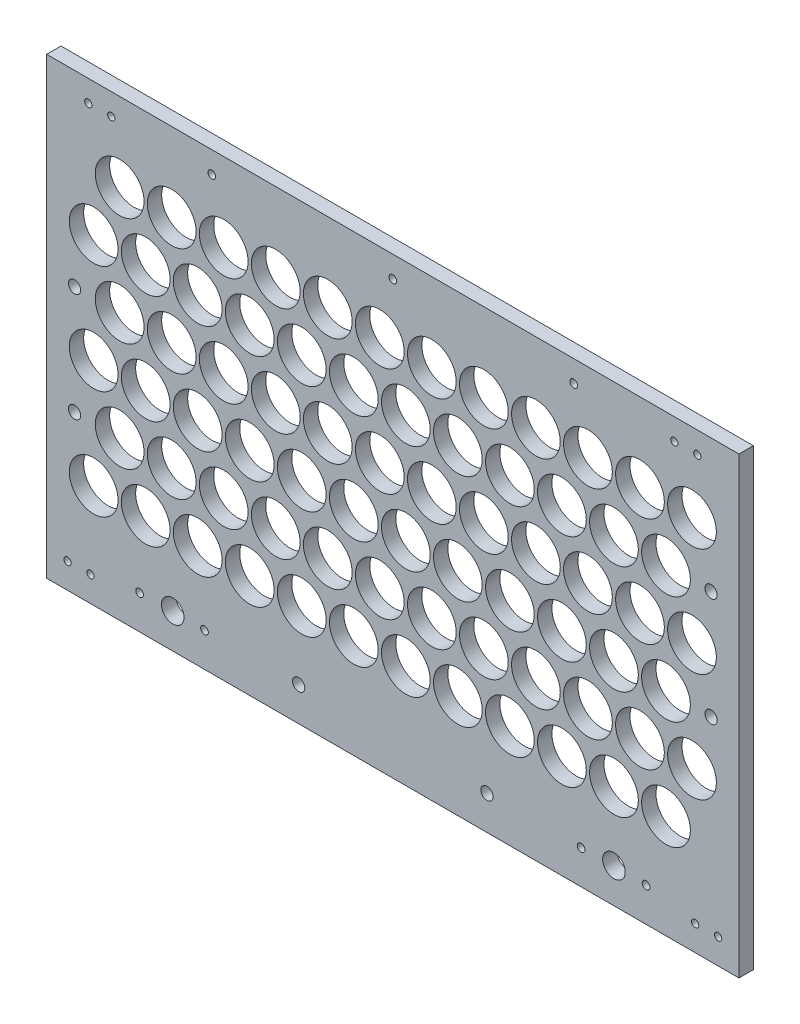
SolidWorks part; units mm, degrees
material "ABS"
ref_plane "X-Y Datum" through (0, 0, 0) normal (0, 0, 1) x (1, 0, 0)
ref_plane "X-Z Datum" through (0, 0, 0) normal (0, 1, 0) x (1, 0, 0)
ref_plane "Y-Z Datum" through (0, 0, 0) normal (1, 0, 0) x (0, 0, -1)
sketch "Sketch1" plane through (0, 0, 0) normal (0, 0, 1) x (1, 0, 0)
  line L1 (-143.025, 70.775) -> (143.025, 70.775)
  line L2 (-143.025, 70.775) -> (-143.025, -70.775)
  line L3 (-143.025, -70.775) -> (143.025, -70.775)
  line L4 (143.025, 70.775) -> (143.025, -70.775)
  line L5 (-143.025, 70.775) -> (143.025, -70.775) construction
  line L6 (-143.025, -70.775) -> (143.025, 70.775) construction
  line L13 (-153.025, -105.775) -> (153.025, -105.775)
  line L14 (-153.025, 91.65) -> (153.025, 91.65)
  line L15 (-153.025, 91.65) -> (-153.025, -105.775)
  line L16 (153.025, 91.65) -> (153.025, -105.775)
  line L17 (153.025, 70.775) -> (153.025, -70.775) construction
  line L18 (-143.025, 91.65) -> (143.025, 91.65) construction
  line L19 (-143.025, -105.775) -> (143.025, -105.775) construction
  line L20 (-153.025, 70.775) -> (-153.025, -70.775) construction
  line L21 (-132.25, -60) -> (-109.25, -60) construction
  circle A0 centre (-132.25, -60) radius 10.775
  circle A1 centre (-109.25, -60) radius 10.775 construction
  circle A2 centre (-120.75, -36) radius 10.775
  point P0 (0, 0)
  point P16 (-120.75, -60)
  dimension "D1" = 21.55
  dimension "D2" = 23
  dimension "D3" = 24
  dimension "D5" = 141.55
  dimension "D6" = 286.05
  dimension "D7" = 35
  dimension "D8" = 20.875
  dimension "D9" = 10
  dimension "D10" = 10
extrude "Boss-Extrude1" add sketch "Sketch1" along normal blind 6.35 contours A0 L3 L4 L1 L2 A2 | A2 | A0 | A0 L2 L3 | L1 L4 L3 L2 region at (2.4105, 0.9241, 0) region at (-140.6182, -68.3682, 0) region at (-132.25, -60, 0) region at (-149.383, -7.0625, 0) region at (-120.75, -36, 0)
sketch "Sketch3" plane through (0, 0, 6.35) normal (0, 0, 1) x (1, 0, 0)
  line L4 (143.025, 70.775) -> (-143.025, 70.775)
  line L5 (143.025, -70.775) -> (143.025, 70.775)
  line L6 (-143.025, -70.775) -> (143.025, -70.775)
  line L7 (-143.025, 70.775) -> (-143.025, -70.775)
  line L8 (143.025, 70.775) -> (-143.025, 70.775)
  line L9 (143.025, -70.775) -> (143.025, 70.775)
  line L10 (-143.025, -70.775) -> (143.025, -70.775)
  line L11 (-143.025, 70.775) -> (-143.025, -70.775)
  circle A1 centre (-120.75, -36) radius 10.775
  circle A2 centre (-120.75, -36) radius 10.775
  circle A3 centre (-132.25, -60) radius 10.775
  circle A4 centre (-132.25, -60) radius 10.775
  dimension "D1" = 0
  dimension "D2" = 0
  dimension "D3" = 0
extrude "Cut-Extrude1" cut sketch "Sketch3" against normal through all contours A4 region at (-132.25, -60, 6.35)
sketch "Sketch4" plane through (0, 0, 6.35) normal (0, 0, 1) x (1, 0, 0)
  line L4 (143.025, 70.775) -> (-143.025, 70.775)
  line L5 (143.025, -70.775) -> (143.025, 70.775)
  line L6 (-143.025, -70.775) -> (143.025, -70.775)
  line L7 (-143.025, 70.775) -> (-143.025, -70.775)
  line L8 (143.025, 70.775) -> (-143.025, 70.775)
  line L9 (143.025, -70.775) -> (143.025, 70.775)
  line L10 (-143.025, -70.775) -> (143.025, -70.775)
  line L11 (-143.025, 70.775) -> (-143.025, -70.775)
  circle A1 centre (-120.75, -36) radius 10.775
  circle A2 centre (-120.75, -36) radius 10.775
  circle A3 centre (-132.25, -60) radius 10.775
  circle A4 centre (-132.25, -60) radius 10.775
  dimension "D1" = 0
  dimension "D2" = 0
  dimension "D3" = 0
extrude "Cut-Extrude2" cut sketch "Sketch4" against normal through all contours A2 region at (-120.75, -36, 6.35)
pattern_linear "LPattern1" count 12 spacing 23 along (1, 0, 0) of "Cut-Extrude1", "Cut-Extrude2"
pattern_linear "LPattern2" count 3 spacing 48 along (0, 1, 0) of "LPattern1"
sketch "Sketch5" plane through (0, 0, 0) normal (0, 0, -1) x (-1, 0, 0)
  circle A0 centre (-97.75, -90.3965) radius 2 construction
  circle A1 centre (-97.75, -90.3965) radius 2 construction
  circle A2 centre (-97.75, -90.3965) radius 5
  circle A3 centre (97.288, -90.3965) radius 5
  point P4 (97.288, -90.3965)
  dimension "D1" = 10
extrude "Cut-Extrude3" cut sketch "Sketch5" against normal through all
sketch "Sketch7" plane through (0, 0, 0) normal (0, 0, -1) x (-1, 0, 0)
  line L0 (0, 3.4925) -> (0, -3.4925) construction
  point P0 (-111.94, -90.775)
  point P1 (-133.6575, -94.6)
  point P3 (-143.8175, -94.6)
  point P5 (-124.45, 85.3)
  point P7 (-134.61, 85.3)
  point P9 (80, 85.3)
  point P11 (0, 85.3)
  point P13 (-80, 85.3)
  point P15 (124.45, 85.3)
  point P17 (134.61, 85.3)
  point P19 (143.8175, -94.6)
  point P21 (133.6575, -94.6)
  point P23 (-83.25, -90.775)
  point P28 (83.25, -90.775)
  point P29 (111.94, -90.775)
hole_wizard "M3 Clearance Hole1" positions "Sketch8" profile "Sketch9" hole size "M3" standard "ANSI Metric" end condition through all
sketch "Sketch8" plane through (0, 0, 0) normal (0, 0, -1) x (-1, 0, 0)
  point P0 (-111.94, -90.775)
  point P3 (80, 85.3)
  point P6 (0, 85.3)
  point P9 (-80, 85.3)
  point P13 (-83.25, -90.775)
  point P17 (111.94, -90.775)
  point P20 (83.25, -90.775)
sketch "Sketch9" plane through (111.94, -90.775, 0) normal (1, 0, 0) x (0, 1, 0)
  line L0 (0, 0) -> (0, 6.35)
  line L1 (0, 6.35) -> (1.7, 6.35)
  line L2 (1.7, 6.35) -> (1.7, 0)
  line L5 (1.7, 0) -> (0, 0)
  line L11 (0, -6.35) -> (0, 107.95) construction
  dimension "Thru Hole Dia." = 3.4
  dimension "Thru Hole Depth" = 6.35
hole_wizard "M3 Clearance Hole2" positions "Sketch10" profile "Sketch11" hole size "M3" standard "ANSI Metric" end condition through all
sketch "Sketch10" plane through (0, 0, 0) normal (0, 0, -1) x (-1, 0, 0)
  point P0 (-143.8175, -94.6)
  point P3 (-133.6575, -94.6)
  point P6 (-134.61, 85.3)
  point P9 (-124.45, 85.3)
  point P12 (124.45, 85.3)
  point P15 (134.61, 85.3)
  point P18 (133.6575, -94.6)
  point P21 (143.8175, -94.6)
sketch "Sketch11" plane through (143.8175, -94.6, 0) normal (1, 0, 0) x (0, 1, 0)
  line L0 (0, 0) -> (0, 6.35)
  line L1 (0, 6.35) -> (1.6, 6.35)
  line L2 (1.6, 6.35) -> (1.6, 0)
  line L5 (1.6, 0) -> (0, 0)
  line L11 (0, -6.35) -> (0, 107.95) construction
  dimension "Thru Hole Dia." = 3.2
  dimension "Thru Hole Depth" = 6.35
sketch "Sketch12" plane through (0, 0, 0) normal (0, 0, -1) x (-1, 0, 0)
  line L0 (83.25, -90.775) -> (-83.25, -90.775) construction
  line L1 (0, -98.7518) -> (0, -82.7982) construction
  line L2 (83.25, -90.775) -> (0, -90.775) construction
  circle A0 centre (41.625, -90.775) radius 2.7
  circle A1 centre (-41.625, -90.775) radius 2.7
  circle A2 centre (140.6875, -36) radius 2.7
  circle A3 centre (-140.6875, 36) radius 2.7
  circle A4 centre (140.6875, 12) radius 2.7
  circle A5 centre (-140.6875, -12) radius 2.7
  point P0 (140.6875, 60)
  point P1 (140.6875, 12)
  point P3 (140.6875, -36)
  point P5 (-140.6875, 36)
  point P7 (-140.6875, -12)
  point P9 (-140.6875, -60)
  point P16 (41.625, -90.775)
  point P20 (0, -90.775)
  dimension "D1" = 5.4
extrude "Cut-Extrude4" cut sketch "Sketch12" against normal through all
sketch "Sketch13" plane through (0, 91.65, 0) normal (0, 1, 0) x (1, 0, 0)
  line L4 (153.025, 0) -> (-153.025, 0)
  line L5 (-153.025, 0) -> (-153.025, -6.35)
  line L6 (-153.025, -6.35) -> (153.025, -6.35)
  line L7 (153.025, -6.35) -> (153.025, 0)
  line L8 (153.025, 0) -> (-153.025, 0)
  line L9 (-153.025, 0) -> (-153.025, -6.35)
  line L10 (-153.025, -6.35) -> (153.025, -6.35)
  line L11 (153.025, -6.35) -> (153.025, 0)
  dimension "D1" = 0
extrude "Boss-Extrude2" add sketch "Sketch13" along normal blind 3.175
